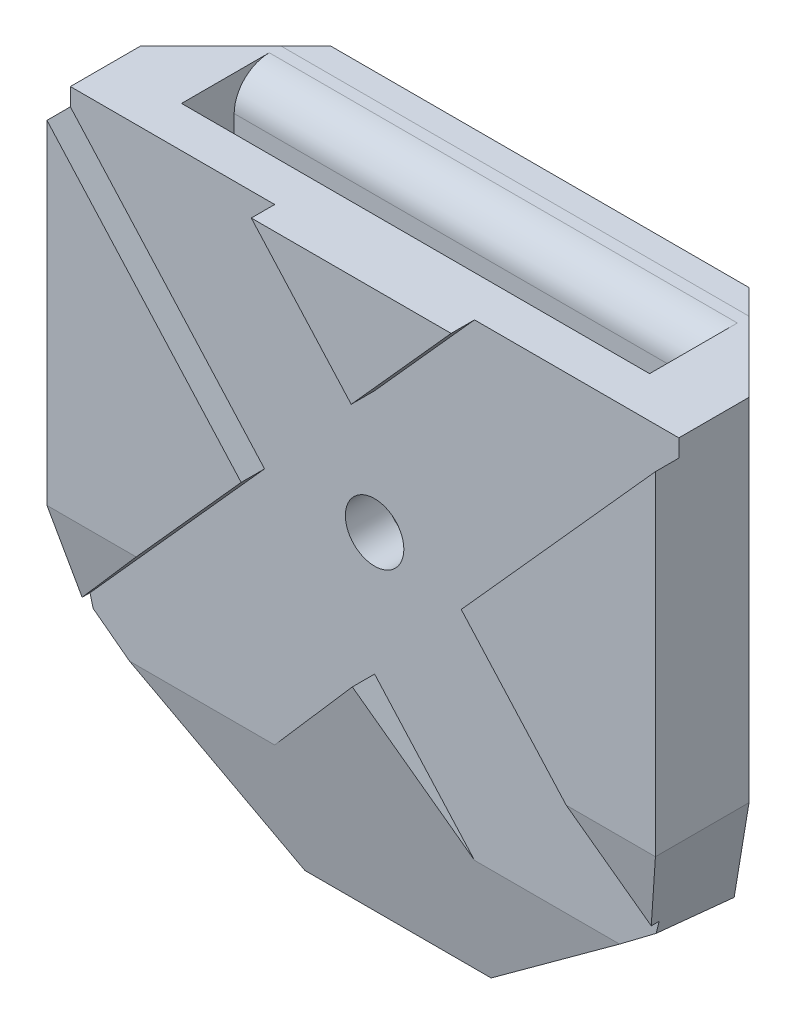
SolidWorks part; units mm, degrees
ref_plane "Спереди" through (0, 0, 0) normal (0, 0, 1) x (1, 0, 0)
ref_plane "Сверху" through (0, 0, 0) normal (0, 1, 0) x (1, 0, 0)
ref_plane "Справа" through (0, 0, 0) normal (1, 0, 0) x (0, 0, -1)
sketch "Эскиз1" plane through (0, 0, 0) normal (0, 1, 0) x (1, 0, 0)
  line L0 (0, 0) -> (3, 0)
  line L1 (26, 0) -> (23, 3)
  line L2 (0, 0) -> (3, 3)
  line L3 (3, 3) -> (23, 3)
  line L4 (3, 0) -> (13, 0)
  line L9 (13, 0) -> (26, 0)
  dimension "D2" = 3
extrude "Бобышка-Вытянуть1" add sketch "Эскиз1" along normal blind 15 and the other way blind 10 draft 6
sketch "Эскиз2" plane through (0, 15, 0) normal (0, 1, 0) x (1, 0, 0)
  line L0 (13, 0) -> (23, 0)
  line L1 (0, 0) -> (26, 0) construction
  line L2 (23, 0) -> (23, 1)
  line L3 (23, 1) -> (3, 1)
  line L4 (3, 1) -> (3, 0)
  line L5 (3, 0) -> (13, 0)
  dimension "D1" = 1
extrude "Вырез-Вытянуть1" cut sketch "Эскиз2" against normal blind 17
sketch "Эскиз4" plane through (0, 0, 0) normal (0, 0, 1) x (1, 0, 0)
  line L0 (0, 15) -> (3, 15)
  line L1 (3, 15) -> (3, -2)
  line L2 (3, -2) -> (23, -2)
  line L3 (23, -2) -> (23, 15)
  line L4 (23, 15) -> (26, 15)
  line L5 (26, 15) -> (26, 0)
  line L6 (26, 0) -> (23.4626, -10)
  line L7 (23.4626, -10) -> (2.5374, -10)
  line L8 (2.5374, -10) -> (0, 0)
  line L9 (0, 0) -> (0, 15)
extrude "Бобышка-Вытянуть2" add sketch "Эскиз4" along normal blind 1
sketch "Эскиз5" plane through (0, 0, 0) normal (0, 0, -1) x (-1, 0, 0)
  line L0 (-26, 0) -> (-23.4626, -10)
  line L1 (-23.4626, -10) -> (-2.5374, -10)
  line L2 (-2.5374, -10) -> (0, 0)
  line L3 (0, 0) -> (-3, 0)
  line L4 (-3, -2) -> (-3, 0)
  line L5 (-3, -2) -> (-3, 15) construction
  line L6 (-3, -2) -> (-3, 15) construction
  line L7 (-3, -2) -> (-23, -2)
  line L8 (-23, -2) -> (-23, 0)
  line L9 (-23, 15) -> (-23, -2) construction
  line L10 (-23, 0) -> (-26, 0)
extrude "Бобышка-Вытянуть3" add sketch "Эскиз5" along normal up to next
sketch "Эскиз6" plane through (0, 0, 1) normal (0, 0, 1) x (1, 0, 0)
  line L0 (0, 15) -> (26, 15)
  line L1 (26, 0) -> (26, 15) construction
  line L2 (26, 15) -> (26, 0)
  line L3 (26, 0) -> (23.4626, -10)
  line L4 (23.4626, -10) -> (2.5374, -10)
  line L5 (2.5374, -10) -> (0, 0)
  line L6 (0, 0) -> (0, 15)
extrude "Бобышка-Вытянуть4" add sketch "Эскиз6" along normal blind 3
sketch "Эскиз7" plane through (26, 0, 0) normal (1, 0, 0) x (0, 0, -1)
  line L0 (-4, 0) -> (-2, -10)
  line L1 (-4, -10) -> (1.051, -10) construction
  line L2 (-2, -10) -> (-4, -10)
  line L3 (-4, -10) -> (-4, 0)
  dimension "D1" = 2
extrude "Вырез-Вытянуть3" cut sketch "Эскиз7" against normal through all
sketch "Эскиз11" plane through (0, 15, 0) normal (0, 1, 0) x (1, 0, 0)
  line L0 (3, 3) -> (4.0607, 4.0607)
  line L1 (23, 3) -> (21.9393, 4.0607)
  line L2 (21.9393, 4.0607) -> (4.0607, 4.0607)
  line L6 (3, 3) -> (23, 3)
extrude "Бобышка-Вытянуть5" add sketch "Эскиз11" against normal blind 15 separate body
chamfer "Фаска2" distance 1.1 distance2 15 1 edges at (13, 0, -4.0607) first distance on face at (13, 0, -3.5303)
sketch "Эскиз3" plane through (0, 0, -1) normal (0, 0, 1) x (1, 0, 0)
  line L0 (13, -2) -> (13, 5)
  circle A0 centre (13, 5) radius 1.25
extrude "Вырез-Вытянуть2" cut sketch "Эскиз3" against normal through all and the other way through all
sketch "Эскиз8" plane through (0, 0, 4) normal (0, 0, 1) x (1, 0, 0)
  line L0 (13, 5) -> (15.6053, 2.6628) construction
  line L1 (2.5374, -10) -> (24.9654, 15) construction
  line L2 (26, 15) -> (0, 15) construction
  line L3 (15.6053, 2.6628) -> (4.2452, -10)
  line L4 (2.5374, -10) -> (23.4626, -10) construction
  line L5 (4.2452, -10) -> (-0.9653, -5.3255)
  line L6 (-0.9653, -5.3255) -> (23.7503, 22.2244)
  line L7 (23.7503, 22.2244) -> (28.9608, 17.55)
  line L8 (28.9608, 17.55) -> (15.6053, 2.6628)
  line L9 (1.3281, 23.2516) -> (-3.8824, 18.5772)
  line L10 (26, 0) -> (23.4626, -10) construction
  line L11 (23.4626, -10) -> (1.0346, 15) construction
  line L12 (1.3281, 23.2516) -> (28.0393, -6.5227)
  line L13 (28.0393, -6.5227) -> (22.8288, -11.1972)
  line L14 (22.8288, -11.1972) -> (2.253, 11.7382)
  line L15 (-3.8824, 18.5772) -> (2.253, 11.7382)
  circle M1 centre (13, 5) radius 1.25
  line M2 (0, 15) -> (0, 0)
  line M3 (0, 0) -> (26, 0)
  line M4 (26, 0) -> (26, 15)
  line M5 (26, 15) -> (0, 15)
extrude "Вырез-Вытянуть6" cut sketch "Эскиз8" against normal blind 1 contours L9 L15 L12 M2 M5 | L15 L14 L6 L12 M2 M5 | L14 L3 L8 L12 L6 M3 M1 | L6 L12 L8 M4 M5 | L14 L13 L12 L3 M3 | L12 L8 L3 M3 | L3 L14 L6 L5 M3 | L14 L6 M3 | L14 L3 M3
sketch "Эскиз9" plane through (0, -0.3119, -2.9672) normal (0, -0.1045, -0.9945) x (-1, 0, 0)
  line L0 (-26.1328, -3.2896) -> (-16.5456, -10.4792)
  line L1 (-16.5456, -10.4792) -> (-26.1328, -10.4792)
  line L2 (-26.1328, -10.4792) -> (-26.1328, -3.2896)
  line L3 (-13, -9.7415) -> (-13, -13.8) construction
  line L4 (-22.5646, -9.7415) -> (-3.4354, -9.7415) construction
  line L5 (0.1328, -10.4792) -> (0.1328, -3.2896)
  line L6 (-9.4544, -10.4792) -> (0.1328, -10.4792)
  line L7 (0.1328, -3.2896) -> (-9.4544, -10.4792)
extrude "Вырез-Вытянуть7" cut sketch "Эскиз9" against normal blind 10
sketch "Эскиз10" plane through (0, 15, 0) normal (0, 1, 0) x (1, 0, 0)
  line L0 (3, 3) -> (4.0607, 4.0607)
  line L1 (23, 3) -> (21.9393, 4.0607)
  line L2 (21.9393, 4.0607) -> (4.0607, 4.0607)
  line L3 (3, 3) -> (23, 3)
fillet "Скругление1" radius 1.5 1 edges at (13, 15, -1)
sketch "Эскиз13" plane through (0, 15, 0) normal (0, 1, 0) x (1, 0, 0)
  line L0 (3, -1) -> (3, -1.25)
  line L1 (3, -1.25) -> (23, -1.25)
  line L2 (23, -1.25) -> (23, -1)
  line L3 (3, -1) -> (23, -1)
extrude "Вырез-Вытянуть8" cut sketch "Эскиз13" against normal up to vertex (17 mm away) up to point (3, -2, 1)
